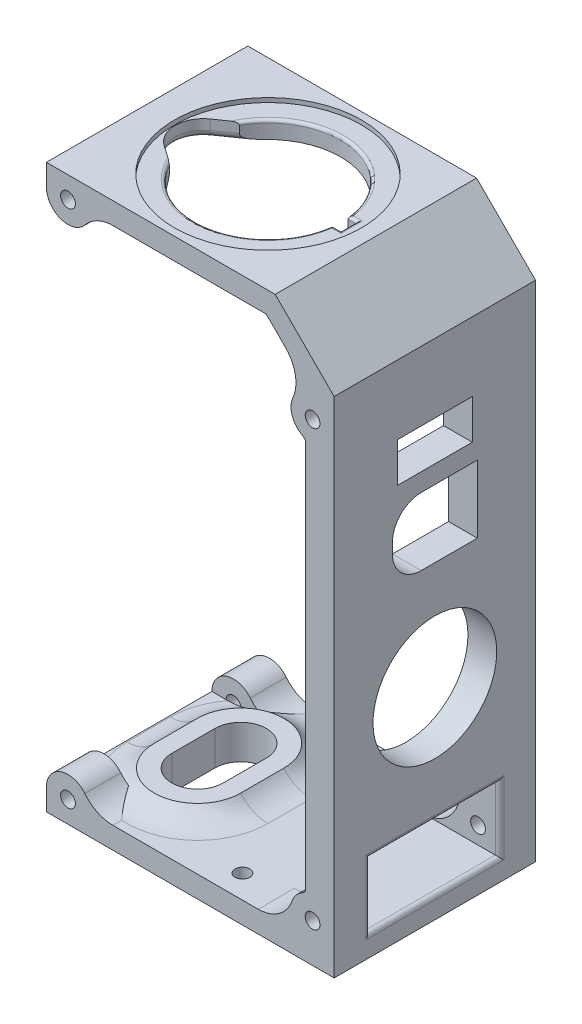
SolidWorks part; units mm, degrees
ref_plane "Front Plane" through (0, 0, 0) normal (0, 0, 1) x (1, 0, 0)
ref_plane "Top Plane" through (0, 0, 0) normal (0, 1, 0) x (1, 0, 0)
ref_plane "Right Plane" through (0, 0, 0) normal (1, 0, 0) x (0, 0, -1)
sketch "Sketch1" plane through (0, 0, 0) normal (0, 0, 1) x (1, 0, 0)
  line L0 (31.8, 78.2) -> (40, 70)
  line L1 (0, 0) -> (40, 0)
  line L3 (0, 78.2) -> (31.8, 78.2)
  line L4 (40, 0) -> (40, 70)
  line L5 (0, 0) -> (0, 3)
  line L6 (6, 75.2) -> (30.5574, 75.2)
  line L7 (35.2, 3) -> (6, 3)
  line L8 (37, 8.4) -> (37, 62.7574)
  line L10 (-74.4457, 75.2) -> (30.5574, 75.2) construction
  line L11 (1.2019, 3) -> (-74.4457, 75.2) construction
  line L12 (30.5574, 75.2) -> (37, 68.7574)
  line L13 (30.5574, 75.2) -> (37, 68.7574) construction
  line L14 (1.2019, 3) -> (37, 3) construction
  line L15 (37, 3) -> (37, 68.7574) construction
  line L16 (0, 78.2) -> (0, 75.2)
  line L17 (-81.934, 78.2) -> (31.8, 78.2) construction
  line L18 (40, 0) -> (40, 70) construction
  line L19 (0, 0) -> (-81.934, 78.2) construction
  arc A0 (37, 68.7574) -> (37, 62.7574) centre (37, 65.7574) ccw
  circle A1 centre (37, 65.7574) radius 1.025
  arc A2 (37, 8.4) -> (35.2, 3) centre (37, 5.4) ccw
  circle A3 centre (37, 5.4) radius 1.025
  arc A4 (6, 3) -> (0, 3) centre (3, 3) ccw
  circle A5 centre (3, 3) radius 1.025
  arc A6 (0, 75.2) -> (6, 75.2) centre (3, 75.2) ccw
  circle A7 centre (3, 75.2) radius 1.025
  dimension "D6" = 6
  dimension "D7" = 2.05
  dimension "D1" = 40
  dimension "D2" = 135
  dimension "D3" = 3
  dimension "D4" = 70
  dimension "D5" = 3
extrude "Boss-Extrude1" add sketch "Sketch1" along normal blind 28
sketch "Sketch2" plane through (0, 78.2, 0) normal (0, 1, 0) x (1, 0, 0)
  line L0 (31.8, -14) -> (-12.3888, -14) construction
  line L1 (31.8, -28) -> (31.8, 0) construction
  circle A0 centre (16.8, -14) radius 13
  dimension "D1" = 26
  dimension "D2" = 15
extrude "Cut-Extrude1" cut sketch "Sketch2" against normal blind 0.6
sketch "Sketch22" plane through (37, 0, 0) normal (-1, 0, 0) x (0, 0, 1)
  line L1 (0, 62.7574) -> (28, 62.7574)
  line L2 (0, 62.7574) -> (0, 8.4)
  line L3 (0, 8.4) -> (28, 8.4)
  line L4 (28, 62.7574) -> (28, 8.4)
extrude "Boss-Extrude5" add sketch "Sketch22" along normal blind 1
sketch "Sketch3" plane through (0, 77.6, 0) normal (0, 1, 0) x (1, 0, 0)
  line L0 (16.8, -14) -> (48.7255, -14) construction
  line L2 (26.8399, -12.9) -> (28.0399, -12.9)
  line L4 (26.8399, -15.1) -> (28.0399, -15.1)
  line L5 (28.0399, -12.9) -> (28.0399, -15.1)
  arc A0 (26.8399, -12.9) -> (26.8399, -15.1) centre (16.8, -14) ccw
  dimension "D1" = 20.2
  dimension "D2" = 1.2
  dimension "D3" = 2.2
extrude "Cut-Extrude2" cut sketch "Sketch3" against normal up to next
fillet "Fillet1" radius 0.4 4 edges at (6.7, 77.6, 14) (27.4399, 77.6, 15.1) (28.0399, 77.6, 14) (27.4399, 77.6, 12.9)
sketch "Sketch14" plane through (40, 0, 0) normal (1, 0, 0) x (0, 0, -1)
  line L0 (-14, 70) -> (-14, 0) construction
  line L1 (-28, 70) -> (0, 70) construction
  line L3 (-14, 28) -> (13.9962, 28) construction
  line L4 (-19.9, 47.7) -> (-5.1, 47.7) construction
  line L5 (-15.9, 52.4) -> (-8.1, 52.4)
  line L6 (-19.9, 48.4) -> (-19.9, 47)
  line L7 (-15.9, 43) -> (-8.1, 43)
  line L8 (-8.1, 52.4) -> (-8.1, 43)
  line L9 (-19.2, 57.65) -> (4.7334, 57.65) construction
  line L10 (-19.2, 60.4) -> (-8.8, 60.4)
  line L11 (-19.2, 60.4) -> (-19.2, 54.9)
  line L12 (-19.2, 54.9) -> (-8.8, 54.9)
  line L13 (-8.8, 60.4) -> (-8.8, 54.9)
  line L14 (-7.325, 47.7) -> (3.1305, 47.7) construction
  line L15 (-28, 0) -> (0, 0) construction
  line L17 (-23, 12) -> (-5, 12)
  line L18 (-23, 12) -> (-23, 3)
  line L19 (-23, 3) -> (-5, 3)
  line L20 (-5, 12) -> (-5, 3)
  circle A0 centre (-14, 28) radius 8.6
  circle A1 centre (-14, 16.9) radius 1.025
  circle A2 centre (-14, 39.1) radius 1.025
  circle A3 centre (-6.3, 47.7) radius 1.025
  circle A4 centre (-21.7, 47.7) radius 1.025
  arc A5 (-15.9, 52.4) -> (-19.9, 48.4) centre (-15.9, 48.4) ccw
  arc A6 (-19.9, 47) -> (-15.9, 43) centre (-15.9, 47) ccw
  circle A7 centre (-23.15, 57.65) radius 1.025
  circle A8 centre (-4.85, 57.65) radius 1.025
  point P27 (-19.9, 52.4)
  point P40 (-19.9, 43)
  dimension "D1" = 17.2
  dimension "D2" = 2.05
  dimension "D7" = 2.05
  dimension "D9" = 4
  dimension "D13" = 2.05
  dimension "D3" = 22.2
  dimension "D4" = 28
  dimension "D5" = 9.4
  dimension "D6" = 11.8
  dimension "D8" = 15.4
  dimension "D10" = 15
  dimension "D11" = 10.4
  dimension "D12" = 5.5
  dimension "D14" = 18.3
  dimension "D15" = 2.5
  dimension "D16" = 18
  dimension "D17" = 3
  dimension "D18" = 9
extrude "Cut-Extrude9" cut sketch "Sketch14" against normal through all
fillet "Fillet2" radius 5 6 edges at (35.2, 3, 25.5) (35.2, 3, 2.5) (37, 68.7574, 14) (6, 3, 25.5) (6, 3, 2.5) (6, 75.2, 14)
ref_plane "Plane1" through (0, 0, 14) normal (0, 0, 1) x (1, 0, 0)
sketch "Sketch16" plane through (0, 0, 14) normal (0, 0, 1) x (1, 0, 0)
  line L0 (1.975, 3) -> (4.025, 3)
  arc A0 (1.975, 3) -> (4.025, 3) centre (3, 3) ccw
  circle A1 centre (3, 3) radius 1.025 construction
extrude "Boss-Extrude2" add sketch "Sketch16" along normal mid plane 18
sketch "Sketch17" plane through (0, 3, 0) normal (0, 1, 0) x (1, 0, 0)
  line L0 (-22, -14) -> (22, -14) construction
  line L2 (10, -17) -> (10, -11) construction
  line L3 (4, -17) -> (4, -11)
  line L4 (16, -17) -> (16, -11)
  line L5 (-1.8935, -14) -> (39.7453, -14) construction
  arc A1 (4, -17) -> (16, -17) centre (10, -17) ccw
  arc A2 (16, -11) -> (4, -11) centre (10, -11) ccw
  point P8 (10, -14)
  dimension "D3" = 6
  dimension "D4" = 6
extrude "Boss-Extrude3" add sketch "Sketch17" along normal blind 1.76
sketch "Sketch18" plane through (0, 4.76, 0) normal (0, 1, 0) x (1, 0, 0)
  line L0 (-1.8826, -14) -> (40.0349, -14) construction
  line L1 (-22, -14) -> (22, -14) construction
  line L2 (10, -17) -> (10, -11) construction
  line L3 (6.43, -17) -> (6.43, -11)
  line L4 (13.57, -17) -> (13.57, -11)
  arc A1 (6.43, -17) -> (13.57, -17) centre (10, -17) ccw
  arc A2 (13.57, -11) -> (6.43, -11) centre (10, -11) ccw
  point P9 (10, -14)
  dimension "D2" = 3.57
  dimension "D3" = 6
extrude "Cut-Extrude10" cut sketch "Sketch18" against normal up to next
fillet "Fillet3" radius 5 4 edges at (4, 3, 14) (10, 3, 5) (16, 3, 14) (10, 3, 23)
sketch "Sketch19" plane through (0, 3, 0) normal (0, 1, 0) x (1, 0, 0)
  line L0 (-1.4647, -14) -> (47.0035, -14) construction
  line L1 (-22, -14) -> (22, -14) construction
  line L2 (29.4343, 0) -> (9.245, 0) construction
  line L3 (40, -22.6) -> (40, -5.4) construction
  line L4 (29.4343, -5) -> (29.4343, 0) construction
  circle A0 centre (24, -3.25) radius 1.025
  circle A1 centre (24, -24.75) radius 1.025
  dimension "D1" = 2.05
  dimension "D3" = 3.25
  dimension "D4" = 16
  dimension "D5" = 5.4343
  dimension "D2" = 21.5
extrude "Cut-Extrude11" cut sketch "Sketch19" against normal up to next
fillet "Fillet4" radius 0.6 5 edges at (36, 12, 14) (40, 7.5, 23) (40, 3, 14) (40, 7.5, 5) (40, 12, 14)
sketch "Sketch20" plane through (0, 0, 0) normal (-1, 0, 0) x (0, 0, 1)
  line L0 (14, 87.38) -> (14, -6.6146) construction
  line L1 (14, -22) -> (14, 22) construction
  line L2 (5, 3) -> (5, 109.2462) construction
  line L3 (23, 3) -> (23, 109.2462) construction
  line L4 (28, 75.2) -> (0, 75.2) construction
  line L5 (23, 75.2) -> (5, 75.2)
  line L6 (23, 75.2) -> (23, 72.2)
  line L7 (23, 72.2) -> (5, 72.2)
  line L8 (5, 75.2) -> (5, 72.2)
  line L9 (0, 72.2) -> (28, 72.2) construction
extrude "Cut-Extrude12" cut sketch "Sketch20" against normal up to next
sketch "Sketch21" plane through (0, 0, 14) normal (0, 0, 1) x (1, 0, 0)
  line L0 (1.975, 75.2) -> (4.025, 75.2)
  arc A0 (4.025, 75.2) -> (1.975, 75.2) centre (3, 75.2) ccw
extrude "Boss-Extrude4" add sketch "Sketch21" along normal mid plane 18
fillet "Fillet6" radius 3 3 edges at (37, 8.4, 2.5) (37, 8.4, 25.5) (37, 62.7574, 14)
sketch "Sketch23" plane through (40, 0, 0) normal (1, 0, 0) x (0, 0, -1)
  circle A0 centre (-23.15, 57.65) radius 1.45
  circle A1 centre (-4.85, 57.65) radius 1.45
  circle A2 centre (-21.7, 47.7) radius 1.45
  circle A3 centre (-6.3, 47.7) radius 1.45
  circle A4 centre (-14, 39.1) radius 1.6
  circle A5 centre (-14, 16.9) radius 1.6
extrude "Boss-Extrude6" add sketch "Sketch23" against normal blind 1
sketch "Sketch24" plane through (0, 78.2, 0) normal (0, 1, 0) x (1, 0, 0)
  line L0 (10.8, -20.8616) -> (10.8, -7.1384)
  line L1 (40, -14) -> (-12.8428, -14) construction
  line L2 (40, -28) -> (40, 0) construction
  line L3 (-22, -14) -> (22, -14) construction
  line L4 (10.8, -7.1384) -> (5.5631, -10.8053)
  line L5 (5.5631, -17.1947) -> (10.8, -20.8616)
  line L6 (0, -28) -> (0, 0) construction
  arc A0 (5.5631, -17.1947) -> (5.5631, -10.8053) centre (7.8, -14) cw
  point P11 (1.0006, -14)
  dimension "D1" = 3.9
  dimension "D4" = 3
  dimension "D2" = 10.8
  dimension "D3" = 55
extrude "Cut-Extrude13" cut sketch "Sketch24" against normal up to next
fillet "Fillet7" radius 1 3 edges at (6.7561, 75.2, 18.0301) (6.7561, 75.2, 9.9699) (3.9, 75.2, 14)
